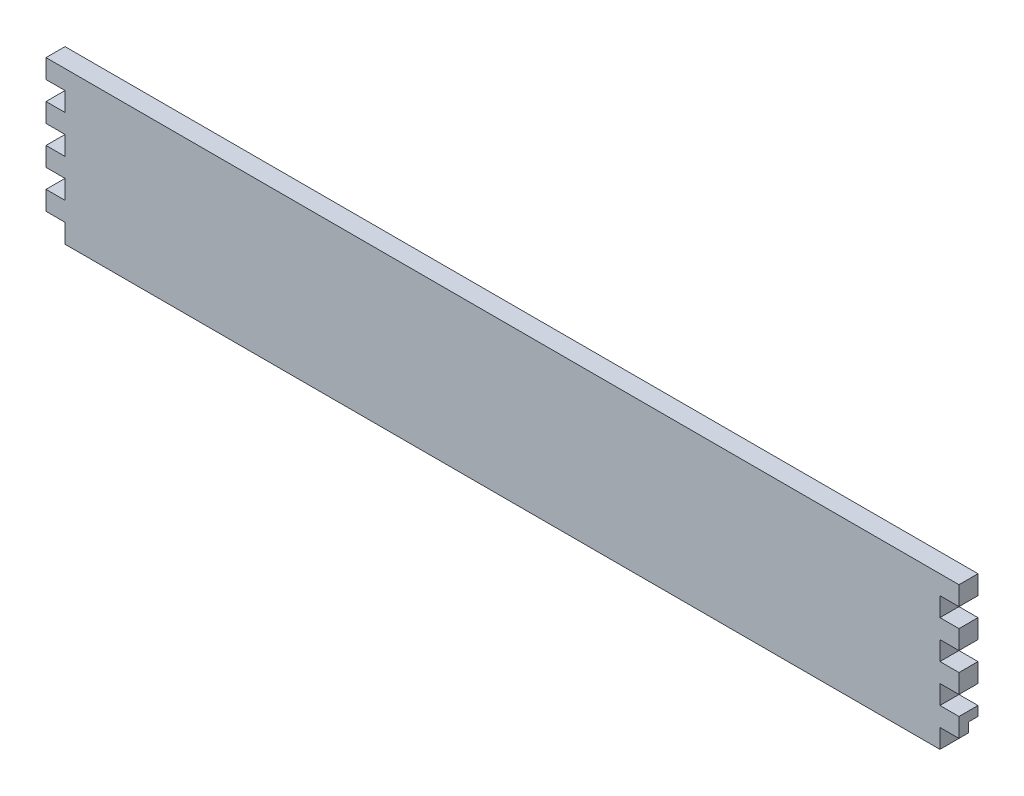
SolidWorks part; units mm, degrees
ref_plane "Front Plane" through (0, 0, 0) normal (0, 0, 1) x (1, 0, 0)
ref_plane "Top Plane" through (0, 0, 0) normal (0, 1, 0) x (1, 0, 0)
ref_plane "Right Plane" through (0, 0, 0) normal (1, 0, 0) x (0, 0, -1)
sketch "Sketch1" plane through (0, 0, 0) normal (0, 0, 1) x (1, 0, 0)
  line L0 (0, 12.7) -> (12.7, 12.7)
  line L1 (12.7, 0) -> (596.9, 0)
  line L2 (0, 12.7) -> (0, 25.4)
  line L3 (0, 101.6) -> (609.6, 101.6)
  line L4 (609.6, 12.7) -> (609.6, 25.4)
  line L5 (12.7, 12.7) -> (12.7, 0)
  line L6 (0, 25.4) -> (12.7, 25.4)
  line L7 (609.6, 12.7) -> (596.9, 12.7)
  line L8 (0, 38.1) -> (12.7, 38.1)
  line L9 (12.7, 38.1) -> (12.7, 25.4)
  line L10 (0, 50.8) -> (12.7, 50.8)
  line L11 (596.9, 12.7) -> (596.9, 0)
  line L12 (0, 63.5) -> (12.7, 63.5)
  line L13 (12.7, 63.5) -> (12.7, 50.8)
  line L14 (0, 76.2) -> (12.7, 76.2)
  line L15 (609.6, 25.4) -> (596.9, 25.4)
  line L16 (0, 88.9) -> (12.7, 88.9)
  line L17 (12.7, 88.9) -> (12.7, 76.2)
  line L18 (0, 101.6) -> (12.7, 101.6)
  line L20 (0, 38.1) -> (0, 50.8)
  line L21 (0, 63.5) -> (0, 76.2)
  line L22 (0, 88.9) -> (0, 101.6)
  line L23 (12.7, 101.6) -> (12.7, 88.9) [skipped]
  line L24 (12.7, 76.2) -> (12.7, 63.5) [skipped]
  line L25 (12.7, 50.8) -> (12.7, 38.1) [skipped]
  line L26 (12.7, 25.4) -> (12.7, 12.7) [skipped]
  line L27 (609.6, 38.1) -> (596.9, 38.1)
  line L28 (596.9, 38.1) -> (596.9, 25.4)
  line L29 (609.6, 50.8) -> (596.9, 50.8)
  line L31 (609.6, 63.5) -> (596.9, 63.5)
  line L32 (596.9, 63.5) -> (596.9, 50.8)
  line L33 (609.6, 76.2) -> (596.9, 76.2)
  line L35 (609.6, 88.9) -> (596.9, 88.9)
  line L36 (596.9, 88.9) -> (596.9, 76.2)
  line L37 (609.6, 101.6) -> (596.9, 101.6)
  line L39 (609.6, 38.1) -> (609.6, 50.8)
  line L40 (609.6, 63.5) -> (609.6, 76.2)
  line L41 (609.6, 88.9) -> (609.6, 101.6)
  line L42 (596.9, 101.6) -> (596.9, 88.9) [skipped]
  line L43 (596.9, 76.2) -> (596.9, 63.5) [skipped]
  line L44 (596.9, 50.8) -> (596.9, 38.1) [skipped]
  line L45 (596.9, 25.4) -> (596.9, 12.7) [skipped]
  dimension "D1" = 101.6
  dimension "D2" = 8
  dimension "D3" = 12.7
  dimension "D4" = 12.7
  dimension "D5" = 12.7
  dimension "D6" = 609.6
  dimension "D7" = 8
extrude "Boss-Extrude1" add sketch "Sketch1" along normal blind 12.7 contours L35 L41 L3 L22 L16 L17 L14 L21 L12 L13 L10 L20 L8 L9 L6 L2 L0 L5 L1 L11 L7 L4 L15 L28 L27 L39 L29 L32 L31 L40 L33 L36 region at (6.35, 19.05, 0) region at (304.8, 50.8, 0) region at (6.35, 44.45, 0) region at (603.25, 19.05, 0) region at (6.35, 69.85, 0) region at (603.25, 44.45, 0) region at (6.35, 95.25, 0) region at (603.25, 69.85, 0) region at (603.25, 95.25, 0)
sketch "Sketch2" plane through (0, 0, 0) normal (0, 0, 1) x (1, 0, 0)
  line L0 (12.7, 0) -> (596.9, 0) construction
  line L1 (626.2823, 19.05) -> (-10.8826, 19.05)
  line L2 (626.2823, 19.05) -> (626.2823, 12.7)
  line L3 (626.2823, 12.7) -> (-10.8826, 12.7)
  line L4 (-10.8826, 19.05) -> (-10.8826, 12.7)
  dimension "D1" = 6.35
  dimension "D2" = 12.7
extrude "Cut-Extrude1" cut sketch "Sketch2" along normal blind 6.35
